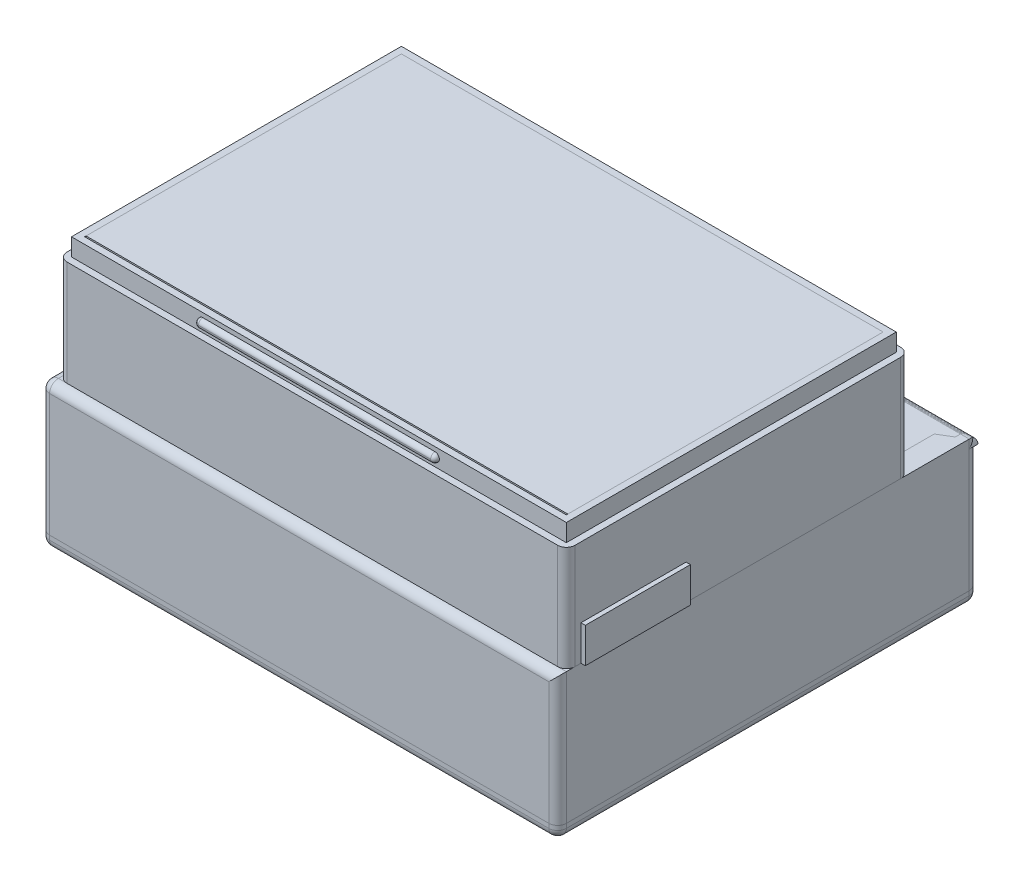
SolidWorks part; units mm, degrees
ref_plane "Front Plane" through (0, 0, 0) normal (0, 0, 1) x (1, 0, 0)
ref_plane "Top Plane" through (0, 0, 0) normal (0, 1, 0) x (1, 0, 0)
ref_plane "Right Plane" through (0, 0, 0) normal (1, 0, 0) x (0, 0, -1)
ref_plane "Plane1" through (0, 15, 0) normal (0, 1, 0) x (1, 0, 0)
sketch "Sketch2" plane through (0, 0, 0) normal (0, 1, 0) x (1, 0, 0)
  line L1 (-27, -21.5) -> (27, -21.5)
  line L2 (-27, -21.5) -> (-27, 21.5)
  line L3 (-27, 21.5) -> (27, 21.5)
  line L4 (27, -21.5) -> (27, 21.5)
  line L5 (-27, -21.5) -> (27, 21.5) construction
  line L6 (-27, 21.5) -> (27, -21.5) construction
  point P0 (0, 0)
  dimension "D1" = 54
  dimension "D2" = 43
extrude "Boss-Extrude1-Battery" add sketch "Sketch2" along normal blind 14
sketch "Sketch4" plane through (0, 15, 0) normal (0, 1, 0) x (1, 0, 0)
  line L1 (-27, -21.3333) -> (28, -21.3333)
  line L2 (-27, -21.3333) -> (-27, 14.6667)
  line L3 (-27, 14.6667) -> (28, 14.6667)
  line L4 (28, -21.3333) -> (28, 14.6667)
  line L5 (-27, -21.3333) -> (28, 14.6667) construction
  line L6 (-27, 14.6667) -> (28, -21.3333) construction
  point P0 (0, 0)
  dimension "D1" = 55
  dimension "D2" = 36
extrude "Boss-Extrude2-Circuit" add sketch "Sketch4" along normal blind 14
sketch "Sketch8" plane through (0, 0, 21.3333) normal (0, 0, 1) x (1, 0, 0)
  line L1 (28, 15) -> (-9, 15)
  line L2 (28, 15) -> (28, 17)
  line L3 (28, 17) -> (-9, 17)
  line L4 (-9, 15) -> (-9, 17)
  line L6 (-9, 17) -> (-9, 15)
  line L7 (-9, 15) -> (-27, 15)
  line L8 (-27, 17) -> (-27, 15)
  line L9 (-27, 17) -> (-17, 17)
  line L10 (-27, 17) -> (-27, 15)
  line L11 (-27, 15) -> (-17, 15)
  line L12 (-17, 17) -> (-17, 15)
  line L13 (-17, 17) -> (-9, 17)
  line L14 (-17, 17) -> (-17, 15)
  line L15 (-17, 15) -> (-9, 15)
  line L16 (-9, 17) -> (-9, 15)
  dimension "D1" = 2
  dimension "D2" = 37
  dimension "D4" = 10
sketch "Sketch11" plane through (28, 0, 0) normal (1, 0, 0) x (0, 0, -1)
  line L0 (14.6667, 29) -> (14.6667, 15) construction
  line L1 (-21.3333, 15) -> (-12.3333, 15)
  line L2 (-21.3333, 15) -> (-21.3333, 17)
  line L3 (-21.3333, 17) -> (-12.3333, 17)
  line L4 (-12.3333, 15) -> (-12.3333, 17)
  line L5 (-12.3333, 15) -> (14.6667, 15)
  line L6 (-12.3333, 15) -> (-12.3333, 17)
  line L7 (-12.3333, 17) -> (14.6667, 17)
  line L8 (14.6667, 15) -> (14.6667, 17)
  line M3 (-21.3333, 15) -> (14.6667, 15)
  line M4 (14.6667, 15) -> (14.6667, 29)
  dimension "D1" = 9
  dimension "D2" = 2
extrude "Cut-Extrude2-CutPins" cut sketch "Sketch11" against normal blind 55 contours L7 L4 M3 M4 region at (28, 16, -1.1667)
sketch "Sketch12" plane through (28, 0, 0) normal (1, 0, 0) x (0, 0, -1)
  line L1 (-21.3333, 15) -> (-9.3333, 15)
  line L2 (-21.3333, 15) -> (-21.3333, 19)
  line L3 (-21.3333, 19) -> (-9.3333, 19)
  line L4 (-9.3333, 15) -> (-9.3333, 19)
  dimension "D1" = 4
  dimension "D2" = 12
extrude "Boss-Extrude1-BatteryCon" add sketch "Sketch12" along normal blind 2
extrude "Cut-Extrude3-SwitchConnGap" cut sketch "Sketch8" against normal blind 10 contours L13 L12 L7 L4 region at (-13, 16, 21.3333)
sketch "Sketch13" plane through (0, 0, 0) normal (0, 1, 0) x (1, 0, 0)
  line L1 (-27, 21.5) -> (27, 21.5)
  line L2 (-27, 21.5) -> (-27, -21.5)
  line L3 (-27, -21.5) -> (27, -21.5)
  line L4 (27, 21.5) -> (27, -21.5)
  line L8 (-29.5, 24) -> (-29.5, -24)
  line L9 (-29.5, -24) -> (29.5, -24)
  line L10 (29.5, 24) -> (29.5, -24)
  line L11 (-29.5, 24) -> (29.5, 24)
  dimension "D1" = 2.5
extrude "Boss-Extrude4" add sketch "Sketch13" along normal blind 15 separate body
ref_plane "Plane2" through (0, 14, 0) normal (0, 1, 0) x (1, 0, 0)
sketch "Sketch14" plane through (0, 14, 0) normal (0, 1, 0) x (1, 0, 0)
  line L0 (-25.5, 13.1667) -> (-25.5, -20)
  line L1 (-29.5, 24) -> (29.5, 24)
  line L2 (-29.5, 24) -> (-29.5, -24)
  line L3 (-29.5, -24) -> (29.5, -24)
  line L4 (29.5, 24) -> (29.5, -24)
  line L5 (-29.5, 24) -> (29.5, 24)
  line L6 (-29.5, 24) -> (-29.5, 14.6667)
  line L7 (-29.5, 14.6667) -> (29.5, 14.6667)
  line L8 (29.5, 24) -> (29.5, 14.6667)
  line L9 (-27, 14.6667) -> (27, 14.6667)
  line L10 (-27, 14.6667) -> (-27, -21.5)
  line L11 (-27, -21.5) -> (27, -21.5)
  line L12 (27, 14.6667) -> (27, -21.5)
  line L13 (-25.5, -20) -> (25.5, -20)
  line L14 (25.5, 13.1667) -> (25.5, -20)
  line L15 (-25.5, 13.1667) -> (25.5, 13.1667)
  line L17 (-27, -12.3333) -> (-17, -12.3333)
  line L18 (-27, -12.3333) -> (-27, -21.5)
  line L19 (-27, -21.5) -> (-17, -21.5)
  line L20 (-17, -12.3333) -> (-17, -21.5)
  line L21 (-8.9929, -12.3333) -> (27, -12.3333)
  line L22 (-8.9929, -12.3333) -> (-8.9929, -21.5)
  line L23 (-8.9929, -21.5) -> (27, -21.5)
  line L24 (27, -12.3333) -> (27, -21.5)
  line L25 (27, -12.3333) -> (25.5, -12.3333)
  line L26 (27, -12.3333) -> (27, -9.3333)
  line L27 (27, -9.3333) -> (25.5, -9.3333)
  line L28 (25.5, -12.3333) -> (25.5, -9.3333)
  line L29 (27, -9.3333) -> (21.2621, -9.3333)
  line L30 (27, -9.3333) -> (27, -21.5)
  line L31 (27, -21.5) -> (21.2621, -21.5)
  line L32 (21.2621, -9.3333) -> (21.2621, -21.5)
  dimension "D2" = 5.7379
  dimension "D1" = 1.5
extrude "Boss-Extrude6" add sketch "Sketch14" along normal blind 3 separate body contours L27 L12 L7 L10 L17 L0 L15 L14 region at (-26.1037, 14, -0.4167)
extrude "Boss-Extrude7" add sketch "Sketch14<6>" along normal blind 1 separate body contours L20 L13 L0 L17 L10 L11 | L32 L13 L22 L11 region at (-25.6357, 14, 16.1667) region at (6.1346, 14, 20.75)
sketch "Sketch14<6>" plane through (0, 14, 0) normal (0, 1, 0) x (1, 0, 0) same geometry as "Sketch14"
extrude "Boss-Extrude9" add sketch "Sketch14<7>" along normal blind 1 separate body contours L2 L7 L4 L1 region at (0, 14, -19.3333)
sketch "Sketch14<7>" plane through (0, 14, 0) normal (0, 1, 0) x (1, 0, 0) same geometry as "Sketch14"
sketch "Sketch15" plane through (0, 15, 0) normal (0, 1, 0) x (1, 0, 0)
  line L0 (-28.5, 16.1667) -> (-28.5, -23)
  line L1 (-27, 14.6667) -> (28, 14.6667)
  line L2 (-27, 14.6667) -> (-27, -21.5)
  line L3 (-27, -21.5) -> (28, -21.5)
  line L4 (28, 14.6667) -> (28, -21.5)
  line L5 (-28.5, -23) -> (29.5, -23)
  line L6 (29.5, 16.1667) -> (29.5, -23)
  line L7 (-28.5, 16.1667) -> (29.5, 16.1667)
  dimension "D1" = 1.5
extrude "Boss-Extrude10" add sketch "Sketch15" along normal blind 14 separate body
sketch "Sketch16" plane through (0, 29, 0) normal (0, 1, 0) x (1, 0, 0)
  line L0 (-27.75, 15.4167) -> (-27.75, -22.25)
  line L1 (-28.5, 16.1667) -> (29.5, 16.1667)
  line L2 (-28.5, 16.1667) -> (-28.5, -23)
  line L3 (-28.5, -23) -> (29.5, -23)
  line L4 (29.5, 16.1667) -> (29.5, -23)
  line L5 (-27.75, -22.25) -> (28.75, -22.25)
  line L6 (28.75, 15.4167) -> (28.75, -22.25)
  line L7 (-27.75, 15.4167) -> (28.75, 15.4167)
  dimension "D1" = 0.75
extrude "Cut-Extrude-LidCut" cut sketch "Sketch16" against normal blind 2
ref_plane "Plane3" through (0, 0, 3.4167) normal (0, 0, -1) x (-1, 0, 0)
sketch "Sketch17" plane through (0, 0, 22.25) normal (0, 0, 1) x (1, 0, 0)
  line L0 (-12.75, 28) -> (13.75, 28) construction
  line L1 (-12.75, 28.5) -> (13.75, 28.5)
  line L2 (-12.75, 27.5) -> (13.75, 27.5)
  line L3 (-27.75, 29) -> (28.75, 29) construction
  line L4 (-28.5, 27) -> (29.5, 27) construction
  line L5 (28.75, 27) -> (28.75, 29) construction
  line L6 (-27.75, 27) -> (-27.75, 29) construction
  arc A0 (-12.75, 28.5) -> (-12.75, 27.5) centre (-12.75, 28) ccw
  arc A1 (13.75, 27.5) -> (13.75, 28.5) centre (13.75, 28) ccw
  point P2 (0.5, 28)
  dimension "D1" = 0.5
  dimension "D2" = 0.5
  dimension "D3" = 15
  dimension "D4" = 15
extrude "Boss-Extrude11" add sketch "Sketch17" along normal blind 0.5
fillet "Fillet5" radius 0.5 4 edges at (14.25, 28, 22.75) (-13.25, 28, 22.75) (0.5, 27.5, 22.75) (0.5, 28.5, 22.75)
mirror "Mirror1" about plane through (0, 0, 3.4167) normal (0, 0, -1) of "Fillet5", "Boss-Extrude11"
sketch "Sketch18" plane through (0, 0, 0) normal (0, -1, 0) x (1, 0, 0)
  line L0 (29.5, 24) -> (29.5, -24) construction
  line L1 (-29.5, 24) -> (29.5, 24)
  line L2 (-29.5, 24) -> (-29.5, -24)
  line L3 (-29.5, -24) -> (29.5, -24)
  line L4 (29.5, 24) -> (29.5, -24)
  line L5 (29.5, -24) -> (-29.5, -24) construction
extrude "Boss-Extrude13" add sketch "Sketch18" along normal blind 1.5 separate body
fillet "Fillet6" radius 1 7 edges at (29.5, 7.5, -24) (29.5, 7.5, 24) (-29.5, 7.5, 24) (-29.5, 7.5, -24) (0, 15, -24) (0, 15, 24) (-29.5, 15, 0)
fillet "Fillet7" radius 1 3 edges at (29.5, 15, -19.3333) (0, 15, -24) (-29.5, 15, -19.3333)
fillet "Fillet8" radius 1 4 edges at (29.5, 21, 23) (29.5, 21, -16.1667) (-28.5, 21, 23) (-28.5, 21, -16.1667)
fillet "Fillet9" radius 1 8 edges at (-29.5, -0.75, -24) (0, -1.5, -24) (-29.5, -0.75, 24) (-29.5, -1.5, 0) (0, -1.5, 24) (29.5, -0.75, 24) (29.5, -1.5, 0) (29.5, -0.75, -24)
